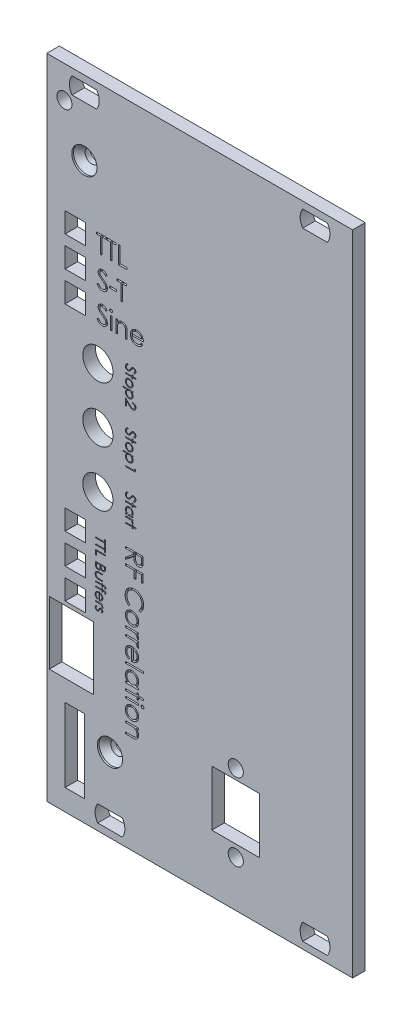
SolidWorks part; units mm, degrees
ref_plane "Front Plane" through (0, 0, 0) normal (0, 0, 1) x (1, 0, 0)
ref_plane "Top Plane" through (0, 0, 0) normal (0, 1, 0) x (1, 0, 0)
ref_plane "Right Plane" through (0, 0, 0) normal (1, 0, 0) x (0, 0, -1)
ref_plane "Plane1" through (0, 0, 2.5) normal (0, 0, 1) x (1, 0, 0)
sketch "Sketch1" plane through (0, 0, 2.5) normal (0, 0, 1) x (1, 0, 0)
  line L0 (53.17, 125.4) -> (-7.45, 125.4)
  line L1 (-7.45, 125.4) -> (-7.45, -3)
  line L2 (-7.45, -3) -> (53.17, -3)
  line L3 (53.17, -3) -> (53.17, 125.4)
  dimension "D1" = 60.62
  dimension "D2" = 128.4
extrude "Boss-Extrude1" add sketch "Sketch1" against normal blind 2.5
sketch "Sketch2" plane through (0, 0, 2.5) normal (0, 0, 1) x (1, 0, 0)
  line L0 (2.4454, 124.05) -> (-2.4454, 124.05)
  line L1 (-2.4454, 120.75) -> (2.4454, 120.75)
  arc A0 (-2.4454, 124.05) -> (-2.4454, 120.75) centre (0, 122.4) ccw
  arc A1 (2.4454, 120.75) -> (2.4454, 124.05) centre (0, 122.4) ccw
extrude "Cut-Extrude1" cut sketch "Sketch2" against normal through all
sketch "Sketch3" plane through (0, 0, 2.5) normal (0, 0, 1) x (1, 0, 0)
  line L0 (7.5254, 1.65) -> (2.6346, 1.65)
  line L1 (2.6346, -1.65) -> (7.5254, -1.65)
  arc A0 (2.6346, 1.65) -> (2.6346, -1.65) centre (5.08, 0) ccw
  arc A1 (7.5254, -1.65) -> (7.5254, 1.65) centre (5.08, 0) ccw
extrude "Cut-Extrude2" cut sketch "Sketch3" against normal through all
sketch "Sketch4" plane through (0, 0, 0) normal (0, 0, -1) x (-1, 0, 0)
  line L0 (3.82, 15.8) -> (-0.08, 15.8)
  line L1 (-0.08, 15.8) -> (-0.08, 1.2)
  line L2 (-0.08, 1.2) -> (3.82, 1.2)
  line L3 (3.82, 1.2) -> (3.82, 15.8)
  line L4 (7.45, 125.4) -> (7.45, -3) construction
  dimension "D1" = 3.63
extrude "Cut-Extrude3" cut sketch "Sketch4" against normal through all
pattern_linear "LPattern2" count 2 spacing 45.72 along (1, 0, 0) count 2 spacing 122.4 along (0, -1, 0) skipping (0, 1) of "Cut-Extrude1"
hole_wizard "Ø3.0 (3) Diameter Hole1" positions "Sketch6" profile "Sketch5" hole size "Ø3.0" standard "ANSI Metric"
sketch "Sketch6" plane through (0, 0, 2.5) normal (0, 0, 1) x (1, 0, 0)
  point P0 (-3.95, 119.1)
sketch "Sketch5" plane through (-3.95, 119.1, 2.5) normal (1, 0, 0) x (0, -1, 0)
  line L0 (0, 0) -> (0, 2.5)
  line L1 (0, 2.5) -> (1.5, 2.5)
  line L2 (1.5, 2.5) -> (1.5, 0)
  line L5 (1.5, 0) -> (0, 0)
  line L11 (0, -6.35) -> (0, 107.95) construction
  dimension "Thru Hole Dia." = 3
  dimension "Thru Hole Depth" = 2.5
hole_wizard "CSK for M2.5 Flat Head Machine Screw1" positions "Sketch8" profile "Sketch7" countersink size "M2.5" standard "ANSI Metric"
sketch "Sketch8" plane through (0, 0, 2.5) normal (0, 0, 1) x (1, 0, 0)
  point P0 (5.08, 11.7)
  point P1 (0, 110.7)
sketch "Sketch7" plane through (5.08, 11.7, 2.5) normal (1, 0, 0) x (0, -1, 0)
  line L0 (0, 0) -> (0, 2.5)
  line L1 (0, 2.5) -> (1.35, 2.5)
  line L2 (1.35, 2.5) -> (1.35, 1.5)
  line L3 (1.35, 1.5) -> (2.5, 0.35)
  line L4 (2.5, 0.35) -> (2.5, 0)
  line L6 (2.5, 0) -> (0, 0)
  line L7 (-1.35, 1.5) -> (-2.5, 0.35) construction
  line L11 (0, -6.35) -> (0, 107.95) construction
  dimension "Thru Hole Dia." = 2.7
  dimension "Thru Hole Depth" = 2.5
  dimension "C'Sink Dia." = 5
  dimension "C'Sink Angle" = 90
  dimension "Head Clearance" = 0.35
ref_plane "Board bottom" through (0, 11.2, 0) normal (0, -1, 0) x (-1, 0, 0)
ref_plane "Board top" through (0, 111.2, 0) normal (0, 1, 0) x (1, 0, 0)
ref_plane "Board upper surface" through (-3.82, 0, 0) normal (1, 0, 0) x (0, 0, -1)
ref_plane "Board lower surface" through (-5.42, 0, 0) normal (1, 0, 0) x (0, 0, -1)
sketch "Sketch9" plane through (0, 0, 2.5) normal (0, 0, 1) x (1, 0, 0)
  line L0 (-3.82, 19.95) -> (-3.82, 32.45) construction
  line L1 (-3.82, 19.95) -> (1.78, 19.95)
  line L2 (-3.82, 32.45) -> (1.78, 32.45)
  line L3 (1.78, 19.95) -> (1.78, 32.45)
  line L4 (-3.82, -47.3899) -> (-3.82, 47.3899) construction
  line L5 (-28.8918, 11.2) -> (28.8918, 11.2) construction
  line L6 (-3.82, 32.45) -> (-3.82, 19.95) construction
  line L7 (-3.82, 32.45) -> (-6.95, 32.45)
  line L8 (-3.82, 19.95) -> (-6.95, 19.95)
  line L9 (-6.95, 32.45) -> (-6.95, 19.95)
  line L10 (-6.95, 32.45) -> (1.78, 19.95) construction
  line L11 (1.78, 32.45) -> (-6.95, 19.95) construction
  line L12 (-7.45, 125.4) -> (-7.45, -3) construction
  point P8 (-2.585, 26.2)
  dimension "D1" = 8.75
  dimension "D2" = 21.25
  dimension "D3" = 5.6
  dimension "D4" = 3.13
  dimension "D5" = 15
  dimension "D6" = 1.235
  dimension "D7" = 12.5
  dimension "D8" = 8.73
  dimension "D9" = 0.5
extrude "USB" cut sketch "Sketch9" against normal through all
sketch "Sketch10" plane through (0, 0, 2.5) normal (0, 0, 1) x (1, 0, 0)
  line L1 (-3.82, 37.2) -> (0.18, 37.2)
  line L2 (-3.82, 37.2) -> (-3.82, 33.2)
  line L3 (-3.82, 33.2) -> (0.18, 33.2)
  line L4 (0.18, 37.2) -> (0.18, 33.2)
  line L5 (-3.82, 37.2) -> (0.18, 33.2) construction
  line L6 (-3.82, 33.2) -> (0.18, 37.2) construction
  line L7 (-3.82, -47.3899) -> (-3.82, 47.3899) construction
  line L8 (-1.82, 35.2) -> (0.18, 35.2) construction
  line L9 (-28.8918, 11.2) -> (28.8918, 11.2) construction
  point P0 (-1.82, 35.2)
  dimension "D1" = 4
  dimension "D2" = 4
  dimension "D3" = 24
  dimension "D4" = 0
extrude "MCXX" cut sketch "Sketch10" against normal through all
pattern_linear "Copy MMCX 1" count 3 spacing 6 along (0, 1, 0) of "MCXX"
pattern_linear "Copy MMCX 2" count 2 spacing 51 along (0, 1, 0) of "Copy MMCX 1"
sketch "Sketch12" plane through (0, 0, 2.5) normal (0, 0, 1) x (1, 0, 0)
  line L0 (-3.82, -47.3899) -> (-3.82, 47.3899) construction
  line L1 (-28.8918, 11.2) -> (28.8918, 11.2) construction
  circle A0 centre (2.68, 55.2) radius 3
  dimension "D1" = 6
  dimension "D2" = 6.5
  dimension "D3" = 44
extrude "Selector 1" cut sketch "Sketch12" against normal through all
pattern_linear "Copy selector" count 3 spacing 11 along (0, 1, 0) of "Selector 1"
sketch "Sketch13" plane through (0, 0, 2.5) normal (0, 0, 1) x (1, 0, 0)
  line L0 (-3.82, 96.2) -> (0.18, 96.2) construction
  line L1 (0.18, 96.2) -> (0.18, 100.2) construction
  text T0 "TTL"
  dimension "D1" = 2.2
extrude "Text TTL" cut sketch "Sketch13" against normal blind 0.5
sketch "Sketch14" plane through (0, 0, 2.5) normal (0, 0, 1) x (1, 0, 0)
  line L7 (-3.82, 90.2) -> (0.18, 90.2) construction
  line L8 (2.4249, 99.341) -> (2.4249, 99.7) construction
  text T0 "S-T"
extrude "Text ST" cut sketch "Sketch14" against normal blind 0.5
sketch "Sketch15" plane through (0, 0, 2.5) normal (0, 0, 1) x (1, 0, 0)
  line L0 (-3.82, 84.2) -> (0.18, 84.2) construction
  line L1 (2.4249, 99.341) -> (2.4249, 99.7) construction
  text T0 "Sine"
extrude "Text Sine" cut sketch "Sketch15" against normal blind 0.5
ref_plane "Text align 2" through (8.17, 0, 0) normal (1, 0, 0) x (0, 0, -1)
sketch "Sketch17" plane through (0, 0, 2.5) normal (0, 0, 1) x (1, 0, 0)
  line L1 (2.68, 69.2) -> (8.17, 69.2) construction
  line L2 (8.17, -1.375) -> (8.17, 1.375) construction
  line L3 (8.17, 69.2) -> (8.17, 59.5505) construction
  circle A0 centre (2.68, 66.2) radius 3 construction
  text T0 "Stop1" font "Century Gothic" height 2
extrude "Cut-Extrude11" cut sketch "Sketch17" against normal blind 0.5
sketch "Sketch18" plane through (0, 0, 2.5) normal (0, 0, 1) x (1, 0, 0)
  line L0 (2.68, 58.2) -> (8.17, 58.2) construction
  line L1 (8.17, -1.375) -> (8.17, 1.375) construction
  line L2 (8.17, 58.2) -> (8.17, 47.8465) construction
  circle A0 centre (2.68, 55.2) radius 3 construction
  text T0 "Start" font "Century Gothic" height 2
extrude "Cut-Extrude12" cut sketch "Sketch18" against normal blind 0.5
sketch "Sketch21" plane through (0, 0, 2.5) normal (0, 0, 1) x (1, 0, 0)
  line L0 (2.68, 80.2) -> (8.17, 80.2) construction
  line L1 (8.17, -1.375) -> (8.17, 1.375) construction
  line L2 (8.17, 80.2) -> (8.17, 70.7585) construction
  circle A0 centre (2.68, 77.2) radius 3 construction
  text T0 "Stop2" font "Century Gothic" height 2
extrude "Cut-Extrude14" cut sketch "Sketch21" against normal blind 0.5
sketch "Sketch23" plane through (0, 0, 2.5) normal (0, 0, 1) x (1, 0, 0)
  line L0 (2.18, 49.2) -> (2.18, 33.2) construction
  line L1 (0.18, 33.2) -> (0.18, 37.2) construction
  line L2 (-3.82, 33.2) -> (0.18, 33.2) construction
  line L3 (0.18, 49.2) -> (-3.82, 49.2) construction
  line L4 (0.18, 39.2) -> (0.18, 43.2) construction
  text T0 "TTL Buffers" font "Century Gothic" height 2
  dimension "D1" = 2
extrude "Cut-Extrude15" cut sketch "Sketch23" against normal blind 0.5
sketch "Sketch24" plane through (0, 0, 2.5) normal (0, 0, 1) x (1, 0, 0)
  line L0 (8.17, 49.2) -> (8.17, 15.9676) construction
  line L1 (8.17, -1.375) -> (8.17, 1.375) construction
  line L2 (0.18, 49.2) -> (-3.82, 49.2) construction
  text T0 "RF Correlation"
extrude "Main title" cut sketch "Sketch24" against normal blind 0.5
sketch "Sketch25" plane through (0, 0, 2.5) normal (0, 0, 1) x (1, 0, 0)
  line L0 (30.0055, 44.9856) -> (30.0055, 34.4856) construction
  line L1 (25.2555, 19.4226) -> (34.7555, 19.4226)
  line L2 (25.2555, 19.4226) -> (25.2555, 8.4226)
  line L3 (25.2555, 8.4226) -> (34.7555, 8.4226)
  line L4 (34.7555, 19.4226) -> (34.7555, 8.4226)
  circle A2 centre (30.0055, 21.4226) radius 1.5
  circle A3 centre (30.0055, 6.1226) radius 1.5
  dimension "D5" = 3
  dimension "D6" = 3
  dimension "D1" = 11
  dimension "D2" = 9.5
  dimension "D3" = 15.3
  dimension "D4" = 13
extrude "Barrel Jack" cut sketch "Sketch25" against normal through all
equation "\"D6@Sketch9\"=2.47/2"
